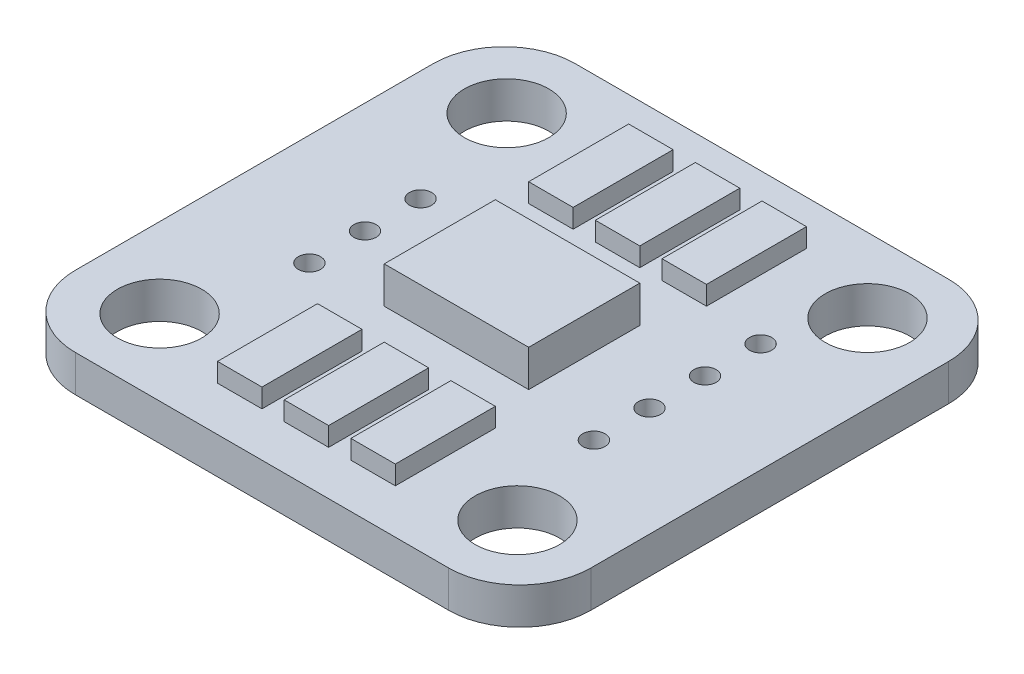
SolidWorks part; units mm, degrees
ref_plane "Front Plane" through (0, 0, 0) normal (0, 0, 1) x (1, 0, 0)
ref_plane "Top Plane" through (0, 0, 0) normal (0, 1, 0) x (1, 0, 0)
ref_plane "Right Plane" through (0, 0, 0) normal (1, 0, 0) x (0, 0, -1)
sketch "Sketch1" plane through (0, 0, 0) normal (0, 1, 0) x (1, 0, 0)
  line L1 (-8.4, -11.25) -> (8.4, -11.25)
  line L2 (-11.6, -8.05) -> (-11.6, 8.05)
  line L3 (-8.4, 11.25) -> (8.4, 11.25)
  line L4 (11.6, -8.05) -> (11.6, 8.05)
  line L5 (-11.6, -11.25) -> (11.6, 11.25) construction
  line L6 (-11.6, 11.25) -> (11.6, -11.25) construction
  line L7 (-8.0152, -7.8409) -> (8.0848, -7.8409) construction
  line L8 (-8.0152, -7.8409) -> (-8.0152, 7.7733) construction
  line L10 (8.0848, -7.8409) -> (8.0848, 7.9091) construction
  line L11 (-8.0152, -7.8409) -> (8.0848, 7.9091) construction
  line L12 (-8.0152, 7.7733) -> (8.0848, -7.8409) construction
  circle A0 centre (-8.0152, 7.7733) radius 1.9
  circle A1 centre (8.0848, 7.9091) radius 1.9
  circle A2 centre (8.0848, -7.8409) radius 1.9
  circle A3 centre (-8.0152, -7.8409) radius 1.9
  arc A4 (-8.4, -11.25) -> (-11.6, -8.05) centre (-8.4, -8.05) cw
  arc A5 (8.4, -11.25) -> (11.6, -8.05) centre (8.4, -8.05) ccw
  arc A6 (8.4, 11.25) -> (11.6, 8.05) centre (8.4, 8.05) cw
  arc A7 (-11.6, 8.05) -> (-8.4, 11.25) centre (-8.4, 8.05) cw
  point P0 (0, 0)
  point P6 (0, 0)
  point P14 (10.2909, -7.4182)
  point P15 (0, 0)
  point P16 (8.1091, -6.1818)
  point P20 (8.1128, -9.3818)
  point P21 (-9.1273, 5.0182)
  point P22 (0, 0)
  point P23 (0, 0)
  point P24 (0, 0)
  point P25 (0, 0)
  point P26 (-6.9957, 5.2586)
  dimension "D5" = 3.8
  dimension "D6" = 3.2
  dimension "D1" = 23.2
  dimension "D2" = 22.5
  dimension "D3" = 15.75
  dimension "D4" = 16.1
extrude "Boss-Extrude1" add sketch "Sketch1" along normal blind 1.65
sketch "Sketch3" plane through (0, 1.65, 0) normal (0, 1, 0) x (1, 0, 0)
  line L0 (0, 11.25) -> (0, -11.25) construction
  line L1 (8.4, 11.25) -> (-8.4, 11.25) construction
  line L2 (-8.4, -11.25) -> (8.4, -11.25) construction
  line L3 (2, 4.75) -> (4, 4.75)
  line L4 (-1, 4.75) -> (1, 4.75)
  line L5 (-1, 4.75) -> (-1, 9.25)
  line L6 (-1, 9.25) -> (1, 9.25)
  line L7 (1, 4.75) -> (1, 9.25)
  line L8 (-1, 4.75) -> (1, 9.25) construction
  line L9 (-1, 9.25) -> (1, 4.75) construction
  line L10 (2, 4.75) -> (2, 9.25)
  line L11 (2, 9.25) -> (4, 9.25)
  line L12 (4, 4.75) -> (4, 9.25)
  line L13 (2, 4.75) -> (4, 9.25) construction
  line L14 (2, 9.25) -> (4, 4.75) construction
  line L15 (-2, 9.25) -> (-4, 4.75) construction
  line L16 (-2, 4.75) -> (-4, 9.25) construction
  line L17 (-4, 4.75) -> (-4, 9.25)
  line L18 (-2, 9.25) -> (-4, 9.25)
  line L19 (-2, 4.75) -> (-2, 9.25)
  line L20 (-2, 4.75) -> (-4, 4.75)
  line L21 (-11.6, 0) -> (11.6, 0) construction
  line L22 (-11.6, 8.05) -> (-11.6, -8.05) construction
  line L23 (11.6, -8.05) -> (11.6, 8.05) construction
  line L24 (-2, -4.75) -> (-4, -9.25) construction
  line L25 (-2, -9.25) -> (-4, -4.75) construction
  line L26 (2, -9.25) -> (4, -4.75) construction
  line L27 (2, -4.75) -> (4, -9.25) construction
  line L28 (-1, -9.25) -> (1, -4.75) construction
  line L29 (-1, -4.75) -> (1, -9.25) construction
  line L30 (-2, -4.75) -> (-4, -4.75)
  line L31 (-2, -4.75) -> (-2, -9.25)
  line L32 (-2, -9.25) -> (-4, -9.25)
  line L33 (-4, -4.75) -> (-4, -9.25)
  line L34 (4, -4.75) -> (4, -9.25)
  line L35 (2, -9.25) -> (4, -9.25)
  line L36 (2, -4.75) -> (2, -9.25)
  line L37 (1, -4.75) -> (1, -9.25)
  line L38 (-1, -9.25) -> (1, -9.25)
  line L39 (-1, -4.75) -> (-1, -9.25)
  line L40 (-1, -4.75) -> (1, -4.75)
  line L41 (2, -4.75) -> (4, -4.75)
  point P6 (0, 7)
  point P11 (3, 7)
  point P20 (-3, 7)
  point P39 (-3, -7)
  point P40 (3, -7)
  point P41 (0, -7)
  dimension "D1" = 2
  dimension "D2" = 4.5
  dimension "D3" = 2
  dimension "D5" = 6
  dimension "D4" = 2
extrude "Boss-Extrude2" add sketch "Sketch3" along normal offset from surface (0.85 mm away) 2.5 contours L20 L19 L18 L17 | L4 L7 L6 L5 | L3 L12 L11 L10 | L41 L36 L35 L34 | L40 L39 L38 L37 | L30 L33 L32 L31 region at (3, 1.65, -7) region at (0, 1.65, -7) region at (-3, 1.65, -7) region at (-3, 1.65, 7) region at (3, 1.65, 7) region at (0, 1.65, 7) up to face at (8.0848, 0, 9.7409)
sketch "Sketch4" plane through (0, 1.65, 0) normal (0, 1, 0) x (1, 0, 0)
  line L1 (-3.25, -2.5) -> (3.25, -2.5)
  line L2 (-3.25, -2.5) -> (-3.25, 2.5)
  line L3 (-3.25, 2.5) -> (3.25, 2.5)
  line L4 (3.25, -2.5) -> (3.25, 2.5)
  line L5 (-3.25, -2.5) -> (3.25, 2.5) construction
  line L6 (-3.25, 2.5) -> (3.25, -2.5) construction
  point P0 (0, 0)
  dimension "D1" = 6.5
  dimension "D2" = 5
extrude "Boss-Extrude3" add sketch "Sketch4" along normal offset from surface (1.65 mm away) 3.3 up to face at (8.0848, 0, 9.7409)
sketch "Sketch5" plane through (0, 1.65, 0) normal (0, 1, 0) x (1, 0, 0)
  line L0 (6.6848, 4.5) -> (6.6848, 2) construction
  line L1 (6.6848, 2) -> (6.6848, -0.5) construction
  line L2 (6.6848, -0.5) -> (6.6848, -3) construction
  line L3 (-6.6152, 2.5) -> (-6.6152, 0) construction
  line L4 (-6.6152, 0) -> (-6.6152, -2.5) construction
  line L5 (6.6848, 2.5) -> (3.25, 2.5) construction
  line L6 (-6.1152, 7.7733) -> (-6.1152, -7.8409) construction
  line L7 (6.1848, 7.9091) -> (6.1848, -7.8409) construction
  circle A0 centre (-6.6152, 0) radius 0.5
  circle A1 centre (-6.6152, 2.5) radius 0.5
  circle A2 centre (-6.6152, -2.5) radius 0.5
  circle A3 centre (6.6848, 4.5) radius 0.5
  circle A4 centre (6.6848, 2) radius 0.5
  circle A5 centre (6.6848, -0.5) radius 0.5
  circle A6 centre (6.6848, -3) radius 0.5
  circle A7 centre (-8.0152, 7.7733) radius 1.9 construction
  circle A8 centre (-8.0152, -7.8409) radius 1.9 construction
  circle A9 centre (8.0848, 7.9091) radius 1.9 construction
  circle A10 centre (8.0848, -7.8409) radius 1.9 construction
  dimension "D2" = 1
  dimension "D1" = 2.5
extrude "Cut-Extrude1" cut sketch "Sketch5" against normal through all
